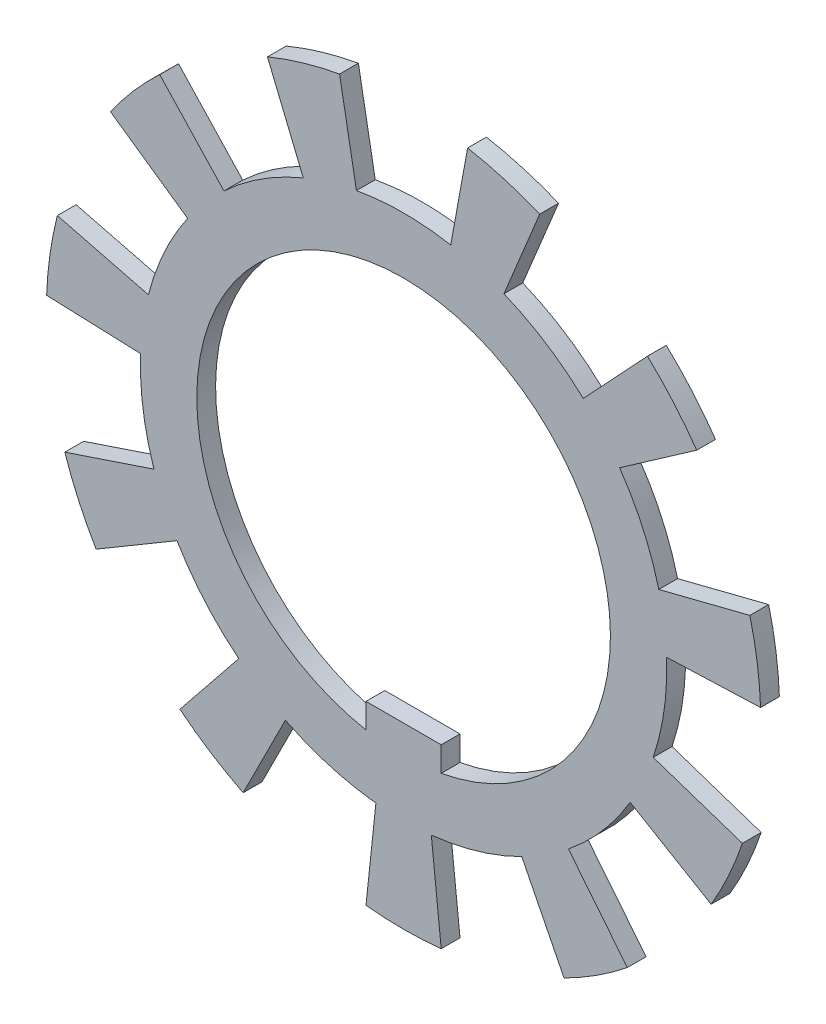
SolidWorks part; units mm, degrees
ref_plane "Front Plane" through (0, 0, 0) normal (0, 0, 1) x (1, 0, 0)
ref_plane "Top Plane" through (0, 0, 0) normal (0, 1, 0) x (1, 0, 0)
ref_plane "Right Plane" through (0, 0, 0) normal (1, 0, 0) x (0, 0, -1)
sketch "BodySke" plane through (0, 0, 0) normal (0, 1, 0) x (1, 0, 0)
  line L0 (0, 0) -> (0, 11) construction
  line L1 (0, 0) -> (4, 0) construction
  line L2 (11, 0) -> (19, 0)
  line L3 (11, 0) -> (11, 1)
  line L4 (11, 1) -> (19, 1)
  line L5 (19, 0) -> (19, 1)
  dimension "Num_tooth" = 11
revolve "BaseBody" add sketch "BodySke" angle 360 about L0
sketch "ToothSke" plane through (0, 0, 0) normal (0, 0, 1) x (1, 0, 0)
  line L0 (0, 0) -> (0, 2.7341) construction
  line L2 (-2.5084, 13.7735) -> (-3.4042, 18.6926)
  line L4 (2.5084, 13.7735) -> (3.4042, 18.6926)
  circle A0 centre (0, 0) radius 14 construction
  arc A1 (-2.5084, 13.7735) -> (2.5084, 13.7735) centre (0, 0) cw
  circle A2 centre (0, 0) radius 11 construction
  circle A3 centre (0, 0) radius 11 construction
  circle A4 centre (0, 0) radius 19 construction
  circle A6 centre (0, 0) radius 19 construction
  arc A7 (-3.4042, 18.6926) -> (3.4042, 18.6926) centre (0, 0) cw
  point P11 (0, 1.083)
  point P12 (0, 14)
  point P15 (0, 2.4103)
  point P16 (0, 19)
  dimension "D2" = 20.643
  dimension "D3" = 6.8084
extrude "ToothCut" cut sketch "ToothSke" against normal through all
pattern_circular "ToothPat" count 11 over 360 about axis through (0, 0, 0) along (0, 0, -1) of "ToothCut"
sketch "LockBodySke" plane through (0, 0, 0) normal (0, 0, 1) x (1, 0, 0)
  line L0 (0, 1.083) -> (0, -20.8872) construction
  line L2 (-2, -9.5) -> (2, -9.5)
  line L3 (-2, -9.5) -> (-2, -11.5)
  line L4 (-2, -11.5) -> (2, -11.5)
  line L5 (2, -9.5) -> (2, -11.5)
  circle A2 centre (0, 0) radius 11 construction
  dimension "D2" = 2
  dimension "D1" = 0.5
extrude "LockBody" add sketch "LockBodySke" against normal up to surface (1 mm away) up to face at (0, 0, -1)
equation "\"Num_tooth@ToothPat\" = \"Num_tooth@BodySke\""
equation "\"D2@ToothSke\" = 360 / \"Num_tooth@BodySke\" - 2 *  arcsin( \"Tooth_width@BodySke\" / \"Outer_dia@BodySke\" ) "
equation "\"D3@ToothSke\" = \"Outer_dia@BodySke\" *  sin( \"D2@ToothSke\" / 2 ) "
equation "\"D2@LockBodySke\" = \"Lock_Width@LockBodySke\" / 2"
